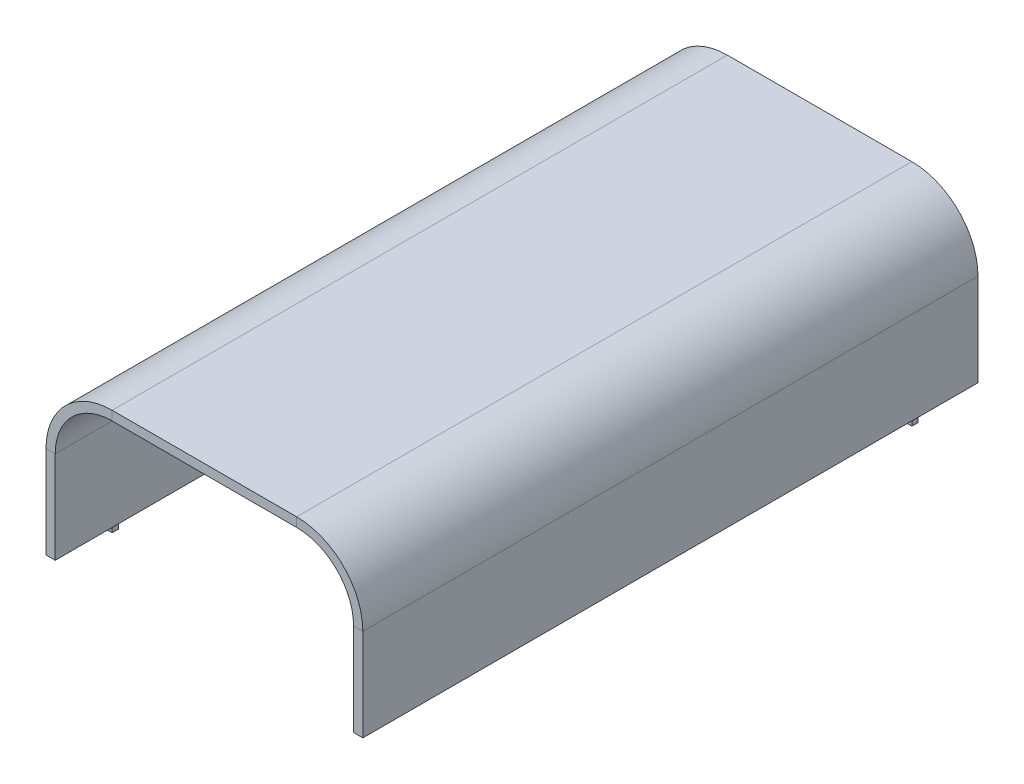
SolidWorks part; units mm, degrees
ref_plane "Front Plane" through (0, 0, 0) normal (0, 0, 1) x (1, 0, 0)
ref_plane "Top Plane" through (0, 0, 0) normal (0, 1, 0) x (1, 0, 0)
ref_plane "Right Plane" through (0, 0, 0) normal (1, 0, 0) x (0, 0, -1)
sketch "Sketch1" plane through (0, 0, 0) normal (0, 0, 1) x (1, 0, 0)
  line L0 (-250, 0) -> (250, 0) construction
  line L1 (-250, 0) -> (-250, 150)
  line L2 (-150, 250) -> (150, 250)
  line L3 (250, 150) -> (250, 0)
  arc A0 (150, 250) -> (250, 150) centre (150, 150) cw
  arc A1 (-250, 150) -> (-150, 250) centre (-150, 150) cw
  point P2 (0, 0)
  point P12 (-250, 250)
  dimension "D3" = 100
  dimension "D1" = 500
  dimension "D2" = 250
sketch "Sketch2" plane through (0, 0, 0) normal (0, 1, 0) x (1, 0, 0)
  line L1 (-257.5, -500) -> (-242.5, -500)
  line L2 (-257.5, -500) -> (-257.5, 500)
  line L3 (-257.5, 500) -> (-242.5, 500)
  line L4 (-242.5, -500) -> (-242.5, 500)
  line L5 (-257.5, -500) -> (-242.5, 500) construction
  line L6 (-257.5, 500) -> (-242.5, -500) construction
  point P0 (-250, 0)
  dimension "D1" = 1000
  dimension "D2" = 15
sweep "Sweep1" add profiles "Sketch2" path "Sketch1"
sketch "Sketch3" plane through (0, 0, 0) normal (0, -1, 0) x (1, 0, 0)
  line L0 (0, 0) -> (-304.363, 0) construction
  line L1 (-250, 500) -> (-250, -500) construction
  line L2 (-257.5, 500) -> (-242.5, 500) construction
  line L3 (-242.5, -500) -> (-257.5, -500) construction
  line L4 (250, -500) -> (250, 500) construction
  line L5 (242.5, -500) -> (257.5, -500) construction
  line L6 (257.5, 500) -> (242.5, 500) construction
  line L7 (-250, 400) -> (250, 400) construction
  line L8 (-255, 405) -> (-245, 405)
  line L9 (-255, 405) -> (-255, 395)
  line L10 (-255, 395) -> (-245, 395)
  line L11 (-245, 405) -> (-245, 395)
  line L12 (-255, 405) -> (-245, 395) construction
  line L13 (-255, 395) -> (-245, 405) construction
  line L14 (245, 405) -> (255, 405)
  line L15 (245, 405) -> (245, 395)
  line L16 (245, 395) -> (255, 395)
  line L17 (255, 405) -> (255, 395)
  line L18 (245, 405) -> (255, 395) construction
  line L19 (245, 395) -> (255, 405) construction
  line L20 (245, -395) -> (255, -395)
  line L21 (245, -395) -> (245, -405)
  line L22 (245, -405) -> (255, -405)
  line L23 (255, -395) -> (255, -405)
  line L24 (245, -395) -> (255, -405) construction
  line L25 (245, -405) -> (255, -395) construction
  line L26 (-255, -395) -> (-245, -395)
  line L27 (-255, -395) -> (-255, -405)
  line L28 (-255, -405) -> (-245, -405)
  line L29 (-245, -395) -> (-245, -405)
  line L30 (-255, -395) -> (-245, -405) construction
  line L31 (-255, -405) -> (-245, -395) construction
  line L32 (250, -400) -> (-250, -400) construction
  line L33 (0, -400) -> (0, 400) construction
  point P16 (-250, 400)
  point P21 (250, 400)
  point P26 (250, -400)
  point P31 (-250, -400)
  dimension "D1" = 800
  dimension "D2" = 10
extrude "Boss-Extrude1" add sketch "Sketch3" along normal blind 10 contours L11 L8 L9 L10 | L23 L20 L21 L22 region at (-250, 0, 400) region at (250, 0, -400)
extrude "Cut-Extrude1" cut sketch "Sketch3<3>" against normal blind 10 contours L29 L26 L27 L28 | L14 L17 L16 L15 region at (-250, 0, -400)
sketch "Sketch3<3>" plane through (0, 0, 0) normal (0, -1, 0) x (1, 0, 0) same geometry as "Sketch3"
